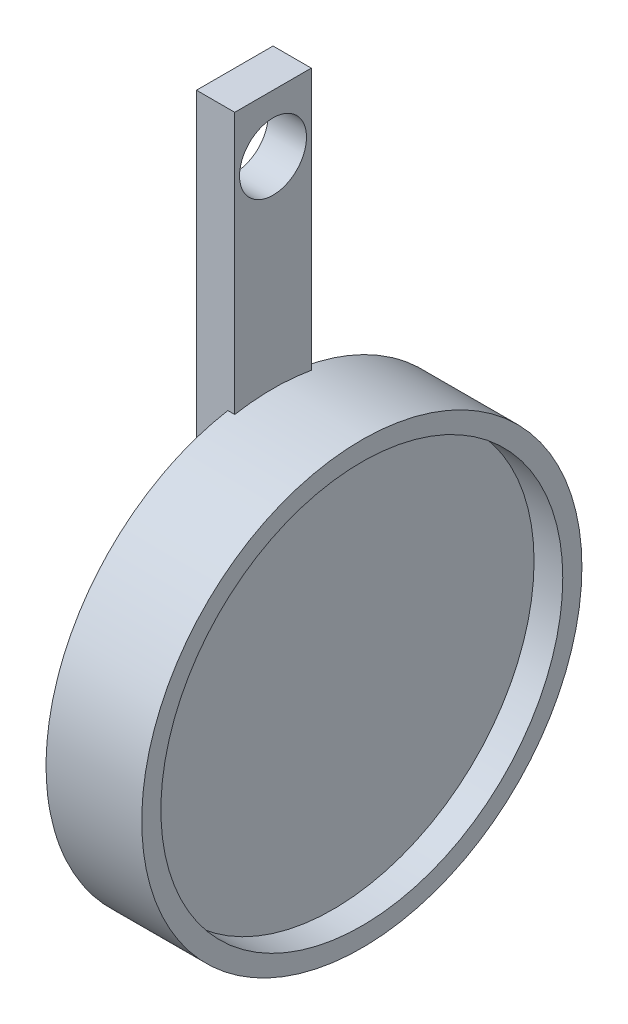
SolidWorks part; units mm, degrees
material "PLA"
ref_plane "Front Plane" through (0, 0, 0) normal (1, 0, 0) x (0, 1, 0)
ref_plane "Top Plane" through (0, 0, 0) normal (0, 0, 1) x (0, 1, 0)
ref_plane "Right Plane" through (0, 0, 0) normal (0, 1, 0) x (-1, 0, 0)
sketch "Sketch1" plane through (0, 0, 0) normal (1, 0, 0) x (0, 1, 0)
  circle A0 centre (0, 0) radius 11.5
  circle A1 centre (0, 0) radius 10.5
  dimension "D1" = 1
  dimension "D2" = 21
extrude "Boss-Extrude1" add sketch "Sketch1" along normal blind 5
extrude "Boss-Extrude2" add sketch "Sketch1<2>" along normal blind 3.5 contours A1 region at (0, 0, 0)
sketch "Sketch1<2>" plane through (0, 0, 0) normal (1, 0, 0) x (0, 1, 0) same geometry as "Sketch1"
ref_plane "Plane1" through (-1.64, 0, 0) normal (-1, 0, 0) x (0, 0, 1)
sketch "Sketch2" plane through (-1.64, 0, 0) normal (-1, 0, 0) x (0, 0, 1)
  line L1 (-2, -5) -> (2, -5)
  line L2 (-2, -5) -> (-2, 5)
  line L3 (-2, 5) -> (2, 5)
  line L4 (2, -5) -> (2, 5)
  line L5 (0, 5) -> (0, -5) construction
  line L6 (-2, 0) -> (2, 0) construction
  point P0 (0, 0)
  dimension "D1" = 4
  dimension "D2" = 10
sketch "Sketch3" plane through (0, 0, 0) normal (-1, 0, 0) x (0, -1, 0)
  circle A0 centre (0, 0) radius 11.5
  circle A1 centre (0, 0) radius 9.5
  circle A2 centre (0, 0) radius 11.5 construction
  dimension "D1" = 2
extrude "Cut-Extrude2" cut sketch "Sketch3" against normal blind 1.5 contours A1 region at (0, 0, 0)
sketch "Sketch4" plane through (0, 0, 0) normal (-1, 0, 0) x (0, -1, 0)
  circle A1 centre (0, 0) radius 11.5
  circle A2 centre (0, 0) radius 11.5
  dimension "D1" = 0
loft "Loft1" add profiles "Sketch4", "Sketch2" connector at (0, 0, 11.5) connector at (-1.64, -5, -2)
sketch "Sketch6" plane through (-1.64, 0, 0) normal (-1, 0, 0) x (0, -1, 0)
  line L0 (0, 0) -> (-22, 0) construction
  line L1 (5, 2) -> (-25, 2)
  line L2 (-25, 2) -> (-25, -2)
  line L3 (-25, -2) -> (5, -2)
  line L4 (5, -2) -> (5, 2)
  circle A1 centre (-22, 0) radius 1.75
  dimension "D2" = 3.5
  dimension "D1" = 22
  dimension "D3" = 3
extrude "Boss-Extrude3" add sketch "Sketch6" against normal blind 2
